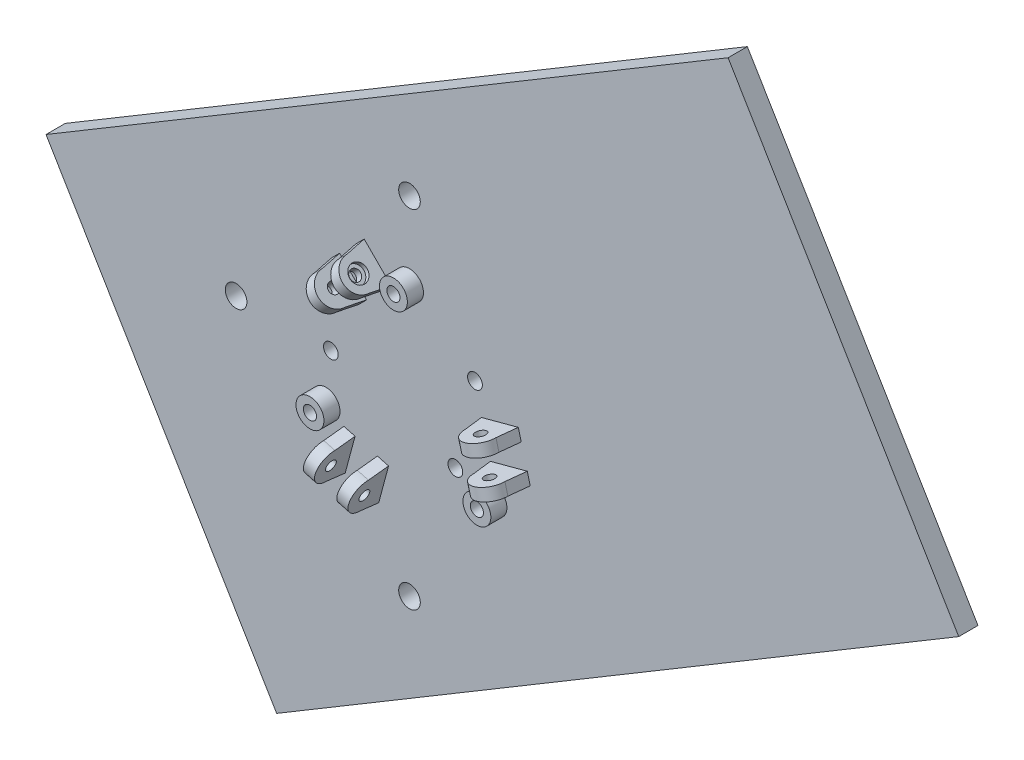
SolidWorks part; units mm, degrees
ref_plane "Front Plane" through (0, 0, 0) normal (0, 0, 1) x (1, 0, 0)
ref_plane "Top Plane" through (0, 0, 0) normal (0, 1, 0) x (1, 0, 0)
ref_plane "Right Plane" through (0, 0, 0) normal (1, 0, 0) x (0, 0, -1)
sketch "S01 - Rounded V3 backplate with cage and cassette fixings" plane through (0, 0, 0) normal (0, 0, 1) x (1, 0, 0)
  line L0 (-113.1634, 13.9297) -> (41.3567, 106.2526)
  line L5 (-113.1634, 13.9297) -> (-41.3567, -106.2526)
  line L7 (-41.3567, -106.2526) -> (113.1634, -13.9297)
  line L8 (-113.1634, 13.9297) -> (113.1634, -13.9297) construction
  line L9 (41.3567, 106.2526) -> (-41.3567, -106.2526) construction
  line L10 (41.3567, 106.2526) -> (99.1896, 140.8067)
  line L11 (99.1896, 140.8067) -> (170.9963, 20.6243)
  line L12 (170.9963, 20.6243) -> (113.1634, -13.9297)
  circle A7 centre (0, 54) radius 3.3651
  circle A8 centre (-53.9735, 0) radius 3.3651
  circle A9 centre (0, -54) radius 3.3651
  circle A10 centre (14.2762, -12.2367) radius 2.2944
  circle A11 centre (20.3946, 14.2762) radius 2.2944
  circle A12 centre (-24.4735, 0) radius 2.2944
  point P1 (0, 0)
  point P3 (0, 0)
  dimension "D2" = 180
  dimension "D3" = 54
  dimension "D4" = 6.7302
  dimension "D5" = 4.5888
  dimension "D6" = 20.3946
  dimension "D7" = 14.2762
  dimension "D8" = 4.5888
  dimension "D9" = 14.2762
  dimension "D10" = 12.2367
  dimension "D11" = 24.4735
  dimension "D12" = 4.5888
  dimension "D13" = 29.5
  dimension "D14" = 6.7302
  dimension "D16" = 6.7302
  dimension "D15" = 54
  dimension "D17" = 140
  dimension "D18" = 113.1634
  dimension "D19" = 106.2526
  dimension "D20" = 67.3693
extrude "01 - Rounded V3 backplate with cage and cassette fixings" add sketch "S01 - Rounded V3 backplate with cage and cassette fixings" along normal blind 6 from offset 12 offset against normal yes
sketch "S02 - Three cord guide pedestals" plane through (0, 0, 0) normal (0, 0, 1) x (1, 0, 0)
  circle A0 centre (25.9808, -15) radius 4.35
  circle A1 centre (0, 30) radius 4.35
  circle A2 centre (-25.9808, -15) radius 4.35
  dimension "D1" = 8.7
  dimension "D2" = 8.7
  dimension "D3" = 8.7
  dimension "D4" = 25.9808
  dimension "D5" = 25.9808
  dimension "D6" = 30
  dimension "D7" = 15
extrude "02 - Three cord guide pedestals" add sketch "S02 - Three cord guide pedestals" along normal blind 5 from offset 6 offset against normal yes
sketch "S03 - Three smooth grommet seats" plane through (0, 0, 0) normal (0, 0, 1) x (1, 0, 0)
  circle A0 centre (25.9808, -15) radius 2.05
  circle A1 centre (0, 30) radius 2.05
  circle A2 centre (-25.9808, -15) radius 2.05
  dimension "D1" = 4.1
  dimension "D2" = 4.1
  dimension "D3" = 4.1
  dimension "D4" = 25.9808
  dimension "D5" = 25.9808
  dimension "D6" = 30
  dimension "D7" = 15
extrude "03 - Three smooth grommet seats" cut sketch "S03 - Three smooth grommet seats" along normal blind 14 from offset 13 offset against normal yes
sketch3d "Plane points - Integral A1 fork cheek L"
  point P0 (30, 0, 0)
  point P1 (12.6133, -4.6587, 0)
  point P2 (30, 0, 18)
ref_plane "Drilling plane - Integral A1 fork cheek L" through (2.0096, -7.5, 0) normal (-0.2588, 0.9659, 0) x (0.9659, 0.2588, 0)
sketch "S04 - Integral A1 fork cheek L" plane through (2.0096, -7.5, 0) normal (-0.2588, 0.9659, 0) x (0.9659, 0.2588, 0)
  line L0 (35.0778, 7) -> (22.8778, 7)
  line L1 (22.8778, 7) -> (24.0278, 0)
  line L2 (33.9278, 0) -> (35.0778, 7)
  arc A0 (24.0278, 0) -> (33.9278, 0) centre (28.9778, 0) ccw
  dimension "D1" = 4.95
  dimension "D2" = 22.8778
  dimension "D3" = 28.9778
  dimension "D4" = 35.0778
  dimension "D5" = 7
extrude "04 - Integral A1 fork cheek L" add sketch "S04 - Integral A1 fork cheek L" along normal blind 3.6 from offset 7.2 offset against normal yes
sketch3d "Plane points - Integral A1 fork cheek R"
  point P0 (30, 0, 0)
  point P1 (12.6133, -4.6587, 0)
  point P2 (30, 0, 18)
ref_plane "Drilling plane - Integral A1 fork cheek R" through (2.0096, -7.5, 0) normal (-0.2588, 0.9659, 0) x (0.9659, 0.2588, 0)
sketch "S05 - Integral A1 fork cheek R" plane through (2.0096, -7.5, 0) normal (-0.2588, 0.9659, 0) x (0.9659, 0.2588, 0)
  line L0 (35.0778, 7) -> (22.8778, 7)
  line L1 (22.8778, 7) -> (24.0278, 0)
  line L2 (33.9278, 0) -> (35.0778, 7)
  arc A0 (24.0278, 0) -> (33.9278, 0) centre (28.9778, 0) ccw
  dimension "D1" = 4.95
  dimension "D2" = 22.8778
  dimension "D3" = 28.9778
  dimension "D4" = 35.0778
  dimension "D5" = 7
extrude "05 - Integral A1 fork cheek R" add sketch "S05 - Integral A1 fork cheek R" along normal blind 3.6 from offset 3.6
sketch3d "Plane points - A1 pivot through both cheeks"
  point P0 (30, 0, 0)
  point P1 (12.6133, -4.6587, 0)
  point P2 (30, 0, 18)
ref_plane "Drilling plane - A1 pivot through both cheeks" through (2.0096, -7.5, 0) normal (-0.2588, 0.9659, 0) x (0.9659, 0.2588, 0)
sketch "S06 - A1 pivot through both cheeks" plane through (2.0096, -7.5, 0) normal (-0.2588, 0.9659, 0) x (0.9659, 0.2588, 0)
  circle A0 centre (28.9778, 0) radius 1.65
  dimension "D1" = 3.3
  dimension "D2" = 28.9778
extrude "06 - A1 pivot through both cheeks" cut sketch "S06 - A1 pivot through both cheeks" along normal blind 15 from offset 7.5 offset against normal yes
sketch3d "Plane points - A1 recessed pivot screw head"
  point P0 (30, 0, 0)
  point P1 (12.6133, -4.6587, 0)
  point P2 (30, 0, 18)
ref_plane "Drilling plane - A1 recessed pivot screw head" through (2.0096, -7.5, 0) normal (-0.2588, 0.9659, 0) x (0.9659, 0.2588, 0)
sketch "S07 - A1 recessed pivot screw head" plane through (2.0096, -7.5, 0) normal (-0.2588, 0.9659, 0) x (0.9659, 0.2588, 0)
  circle A0 centre (28.9778, 0) radius 2.7
  dimension "D1" = 5.4
  dimension "D2" = 28.9778
extrude "07 - A1 recessed pivot screw head" cut sketch "S07 - A1 recessed pivot screw head" along normal blind 1.5 from offset 7.3 offset against normal yes
sketch3d "Plane points - Integral A2 fork cheek L"
  point P0 (-15, 25.9808, 0)
  point P1 (-2.2721, 13.2528, 0)
  point P2 (-15, 25.9808, 18)
ref_plane "Drilling plane - Integral A2 fork cheek L" through (5.4904, 5.4904, 0) normal (-0.7071, -0.7071, 0) x (-0.7071, 0.7071, 0)
sketch "S08 - Integral A2 fork cheek L" plane through (5.4904, 5.4904, 0) normal (-0.7071, -0.7071, 0) x (-0.7071, 0.7071, 0)
  line L0 (35.0778, 7) -> (22.8778, 7)
  line L1 (22.8778, 7) -> (24.0278, 0)
  line L2 (33.9278, 0) -> (35.0778, 7)
  arc A0 (24.0278, 0) -> (33.9278, 0) centre (28.9778, 0) ccw
  dimension "D1" = 4.95
  dimension "D2" = 22.8778
  dimension "D3" = 28.9778
  dimension "D4" = 35.0778
  dimension "D5" = 7
extrude "08 - Integral A2 fork cheek L" add sketch "S08 - Integral A2 fork cheek L" along normal blind 3.6 from offset 7.2 offset against normal yes
sketch3d "Plane points - Integral A2 fork cheek R"
  point P0 (-15, 25.9808, 0)
  point P1 (-2.2721, 13.2528, 0)
  point P2 (-15, 25.9808, 18)
ref_plane "Drilling plane - Integral A2 fork cheek R" through (5.4904, 5.4904, 0) normal (-0.7071, -0.7071, 0) x (-0.7071, 0.7071, 0)
sketch "S09 - Integral A2 fork cheek R" plane through (5.4904, 5.4904, 0) normal (-0.7071, -0.7071, 0) x (-0.7071, 0.7071, 0)
  line L0 (35.0778, 7) -> (22.8778, 7)
  line L1 (22.8778, 7) -> (24.0278, 0)
  line L2 (33.9278, 0) -> (35.0778, 7)
  arc A0 (24.0278, 0) -> (33.9278, 0) centre (28.9778, 0) ccw
  dimension "D1" = 4.95
  dimension "D2" = 22.8778
  dimension "D3" = 28.9778
  dimension "D4" = 35.0778
  dimension "D5" = 7
extrude "09 - Integral A2 fork cheek R" add sketch "S09 - Integral A2 fork cheek R" along normal blind 3.6 from offset 3.6
sketch3d "Plane points - A2 pivot through both cheeks"
  point P0 (-15, 25.9808, 0)
  point P1 (-2.2721, 13.2528, 0)
  point P2 (-15, 25.9808, 18)
ref_plane "Drilling plane - A2 pivot through both cheeks" through (5.4904, 5.4904, 0) normal (-0.7071, -0.7071, 0) x (-0.7071, 0.7071, 0)
sketch "S10 - A2 pivot through both cheeks" plane through (5.4904, 5.4904, 0) normal (-0.7071, -0.7071, 0) x (-0.7071, 0.7071, 0)
  circle A0 centre (28.9778, 0) radius 1.65
  dimension "D1" = 3.3
  dimension "D2" = 28.9778
extrude "10 - A2 pivot through both cheeks" cut sketch "S10 - A2 pivot through both cheeks" along normal blind 15 from offset 7.5 offset against normal yes
sketch3d "Plane points - A2 recessed pivot screw head"
  point P0 (-15, 25.9808, 0)
  point P1 (-2.2721, 13.2528, 0)
  point P2 (-15, 25.9808, 18)
ref_plane "Drilling plane - A2 recessed pivot screw head" through (5.4904, 5.4904, 0) normal (-0.7071, -0.7071, 0) x (-0.7071, 0.7071, 0)
sketch "S11 - A2 recessed pivot screw head" plane through (5.4904, 5.4904, 0) normal (-0.7071, -0.7071, 0) x (-0.7071, 0.7071, 0)
  circle A0 centre (28.9778, 0) radius 2.7
  dimension "D1" = 5.4
  dimension "D2" = 28.9778
extrude "11 - A2 recessed pivot screw head" cut sketch "S11 - A2 recessed pivot screw head" along normal blind 1.5 from offset 7.3 offset against normal yes
sketch3d "Plane points - Integral A3 fork cheek L"
  point P0 (-15, -25.9808, 0)
  point P1 (-10.3413, -8.5941, 0)
  point P2 (-15, -25.9808, 18)
ref_plane "Drilling plane - Integral A3 fork cheek L" through (-7.5, 2.0096, 0) normal (0.9659, -0.2588, 0) x (0, 0, -1)
sketch "S12 - Integral A3 fork cheek L" plane through (-7.5, 2.0096, 0) normal (0.9659, -0.2588, 0) x (0, 0, -1)
  line L0 (7, -35.0778) -> (7, -22.8778)
  line L1 (7, -22.8778) -> (0, -24.0278)
  line L2 (0, -33.9278) -> (7, -35.0778)
  arc A0 (0, -24.0278) -> (0, -33.9278) centre (0, -28.9778) ccw
  dimension "D1" = 4.95
  dimension "D2" = 7
  dimension "D3" = 22.8778
  dimension "D4" = 28.9778
  dimension "D5" = 35.0778
extrude "12 - Integral A3 fork cheek L" add sketch "S12 - Integral A3 fork cheek L" along normal blind 3.6 from offset 7.2 offset against normal yes
sketch3d "Plane points - Integral A3 fork cheek R"
  point P0 (-15, -25.9808, 0)
  point P1 (-10.3413, -8.5941, 0)
  point P2 (-15, -25.9808, 18)
ref_plane "Drilling plane - Integral A3 fork cheek R" through (-7.5, 2.0096, 0) normal (0.9659, -0.2588, 0) x (0, 0, -1)
sketch "S13 - Integral A3 fork cheek R" plane through (-7.5, 2.0096, 0) normal (0.9659, -0.2588, 0) x (0, 0, -1)
  line L0 (7, -35.0778) -> (7, -22.8778)
  line L1 (7, -22.8778) -> (0, -24.0278)
  line L2 (0, -33.9278) -> (7, -35.0778)
  arc A0 (0, -24.0278) -> (0, -33.9278) centre (0, -28.9778) ccw
  dimension "D1" = 4.95
  dimension "D2" = 7
  dimension "D3" = 22.8778
  dimension "D4" = 28.9778
  dimension "D5" = 35.0778
extrude "13 - Integral A3 fork cheek R" add sketch "S13 - Integral A3 fork cheek R" along normal blind 3.6 from offset 3.6
sketch3d "Plane points - A3 pivot through both cheeks"
  point P0 (-15, -25.9808, 0)
  point P1 (-10.3413, -8.5941, 0)
  point P2 (-15, -25.9808, 18)
ref_plane "Drilling plane - A3 pivot through both cheeks" through (-7.5, 2.0096, 0) normal (0.9659, -0.2588, 0) x (0, 0, -1)
sketch "S14 - A3 pivot through both cheeks" plane through (-7.5, 2.0096, 0) normal (0.9659, -0.2588, 0) x (0, 0, -1)
  circle A0 centre (0, -28.9778) radius 1.65
  dimension "D1" = 3.3
  dimension "D2" = 28.9778
extrude "14 - A3 pivot through both cheeks" cut sketch "S14 - A3 pivot through both cheeks" along normal blind 15 from offset 7.5 offset against normal yes
sketch3d "Plane points - A3 recessed pivot screw head"
  point P0 (-15, -25.9808, 0)
  point P1 (-10.3413, -8.5941, 0)
  point P2 (-15, -25.9808, 18)
ref_plane "Drilling plane - A3 recessed pivot screw head" through (-7.5, 2.0096, 0) normal (0.9659, -0.2588, 0) x (0, 0, -1)
sketch "S15 - A3 recessed pivot screw head" plane through (-7.5, 2.0096, 0) normal (0.9659, -0.2588, 0) x (0, 0, -1)
  circle A0 centre (0, -28.9778) radius 2.7
  dimension "D1" = 5.4
  dimension "D2" = 28.9778
extrude "15 - A3 recessed pivot screw head" cut sketch "S15 - A3 recessed pivot screw head" along normal blind 1.5 from offset 7.3 offset against normal yes
